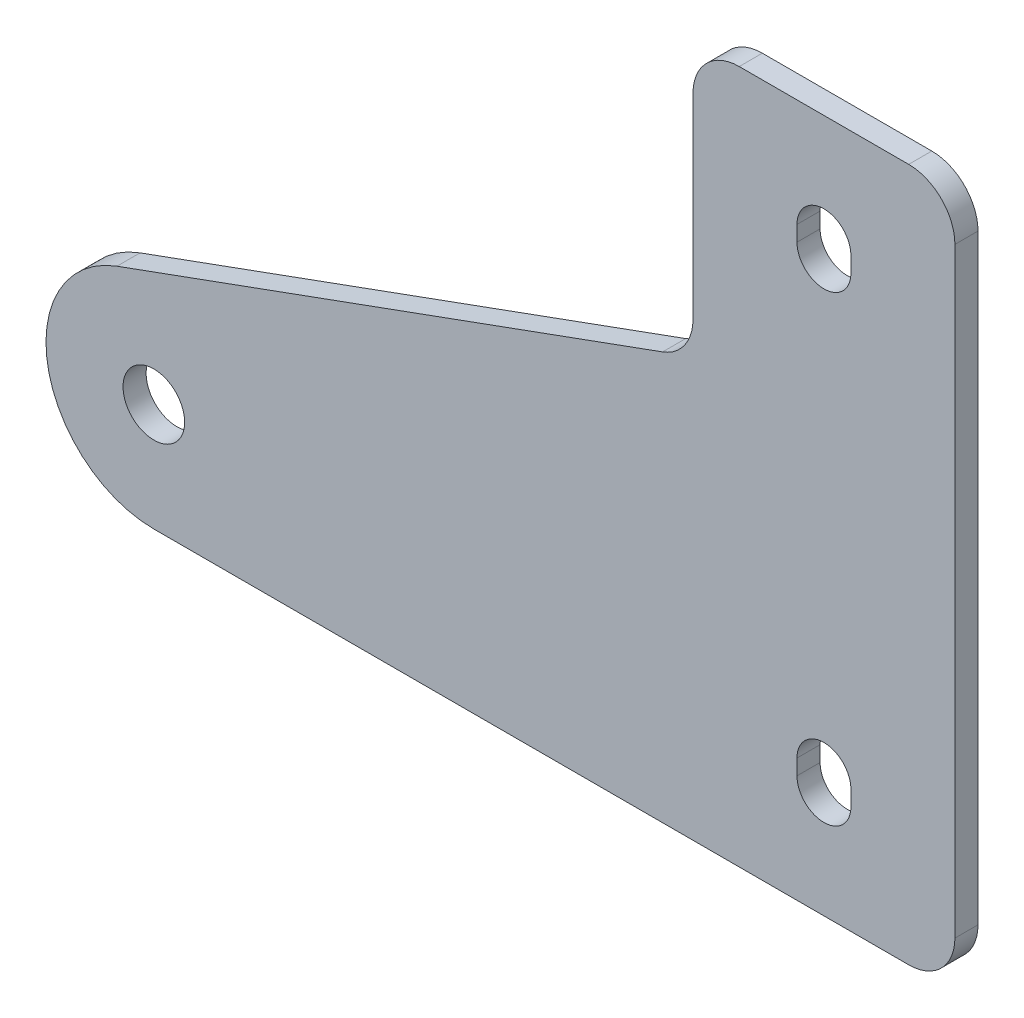
SolidWorks part; units mm, degrees
material "3.3535 (EN-AW 5754)"
ref_plane "Front" through (0, 0, 0) normal (0, 0, 1) x (1, 0, 0)
ref_plane "Top" through (0, 0, 0) normal (0, 1, 0) x (1, 0, 0)
ref_plane "Right" through (0, 0, 0) normal (1, 0, 0) x (0, 0, -1)
sketch "Esquisse1" plane through (0, 0, 0) normal (0, 0, 1) x (1, 0, 0)
  line L0 (0, 0.5) -> (0, -0.5) construction
  line L1 (1.75, 0.5) -> (1.75, -0.5)
  line L2 (-1.75, 0.5) -> (-1.75, -0.5)
  line L3 (0, 30.5) -> (0, 29.5) construction
  line L4 (1.75, 30.5) -> (1.75, 29.5)
  line L5 (-1.75, 30.5) -> (-1.75, 29.5)
  line L7 (-8.5, 37.5) -> (8.5, 37.5)
  line L8 (-8.5, 37.5) -> (-8.5, 19.6882)
  line L9 (-43.5, -7.5) -> (8.5, -7.5)
  line L10 (8.5, 37.5) -> (8.5, -7.5)
  line L11 (-45.8941, 6.0778) -> (-8.5, 19.6882)
  arc A2 (1.75, 0.5) -> (-1.75, 0.5) centre (0, 0.5) ccw
  arc A3 (-1.75, -0.5) -> (1.75, -0.5) centre (0, -0.5) ccw
  arc A4 (1.75, 30.5) -> (-1.75, 30.5) centre (0, 30.5) ccw
  arc A5 (-1.75, 29.5) -> (1.75, 29.5) centre (0, 29.5) ccw
  circle A6 centre (-43.5, -0.5) radius 2
  arc A7 (-45.8941, 6.0778) -> (-43.5, -7.5) centre (-43.5, -0.5) ccw
  point P3 (0, 0)
  point P8 (0, 30)
  point P24 (0, 37.5)
  dimension "D1" = 3.5
  dimension "D2" = 1
  dimension "D4" = 17
  dimension "D5" = 7
  dimension "D6" = 7
  dimension "D7" = 4
  dimension "D8" = 7
  dimension "D9" = 43.5
  dimension "D3" = 30
  dimension "D10" = 20
base flange "Tôle de base pliée1" sketch "Esquisse1" thickness 1.5 reverse thickness direction no parameters "D1"=5
fillet "Congé1" radius 3 4 edges at (-8.5, 19.6882, -0.75) (8.5, -7.5, -0.75) (-8.5, 37.5, -0.75) (8.5, 37.5, -0.75)
sketch "Lignes de pliage1" [suppressed] plane through (0, 0, 0) normal (0, 1, 0) x (1, 0, 0)
sketch "Cube de visualisation1" [suppressed] plane through (0, 0, 0) normal (0, 1, 0) x (1, 0, 0)
sheet metal parameters "Tôlerie1" thickness 1.5 parameters "D1"=5
flat pattern "Etat déplié1" [suppressed]
sketch "Lignes de pliage2" plane through (0, 0, 0) normal (0, 1, 0) x (1, 0, 0)
sketch3d "Cube de visualisation2" [suppressed]
  line L0 (-6.9998, -7, 0) -> (52, -7, 0) construction
  line L1 (-6.9998, 38, 0) -> (52, 38, 0) construction
  line L2 (-6.9998, -7, 0) -> (-6.9998, 38, 0) construction
  line L3 (52, -7, 0) -> (52, 38, 0) construction
